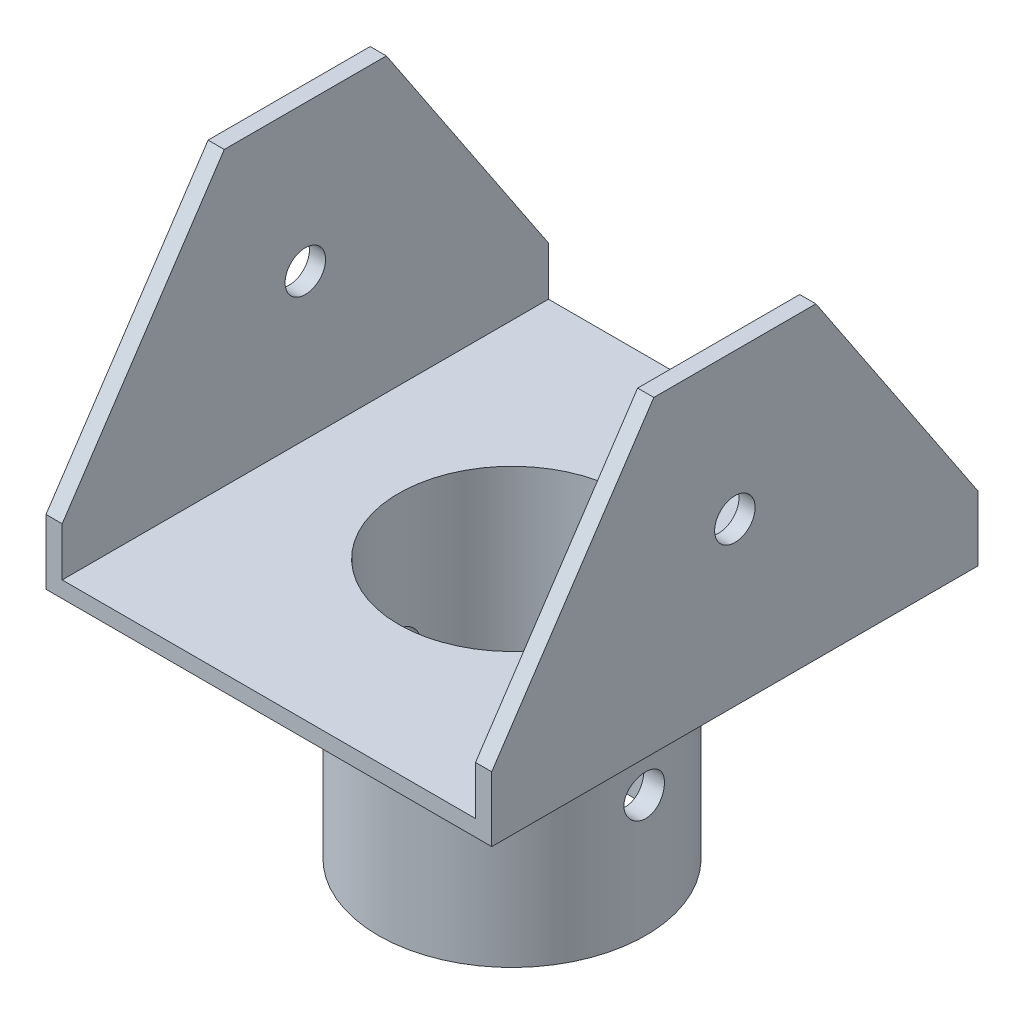
SolidWorks part; units mm, degrees
ref_plane "前视基准面" through (0, 0, 0) normal (0, 0, 1) x (1, 0, 0)
ref_plane "上视基准面" through (0, 0, 0) normal (0, 1, 0) x (1, 0, 0)
ref_plane "右视基准面" through (0, 0, 0) normal (1, 0, 0) x (0, 0, -1)
sketch "草图1" plane through (0, 0, 0) normal (0, 1, 0) x (1, 0, 0)
  circle A0 centre (0, 0) radius 14
  circle A1 centre (0, 0) radius 16.5
  dimension "D1" = 2.5
  dimension "D2" = 33
extrude "凸台-拉伸1" add sketch "草图1" along normal blind 30
sketch "草图2" plane through (0, 0, 0) normal (0, 0, 1) x (1, 0, 0)
  line L0 (0, 0) -> (0, 28.5022) construction
  line L1 (-16.5, 0) -> (16.5, 0) construction
  line L2 (27.5, 30) -> (-27.5, 30)
  line L3 (16.5, 30) -> (-16.5, 30) construction
  line L4 (-27.5, 30) -> (-27.5, 68)
  line L5 (-27.5, 68) -> (-25.5, 68)
  line L6 (-25.5, 68) -> (-25.5, 32)
  line L7 (-25.5, 32) -> (25.5, 32)
  line L9 (27.5, 30) -> (27.5, 68)
  line L10 (27.5, 68) -> (25.5, 68)
  line L11 (25.5, 68) -> (25.5, 32)
  point P13 (0, 32)
  point P14 (0, 30)
  dimension "D1" = 55
  dimension "D2" = 38
  dimension "D3" = 2
  dimension "D4" = 2
extrude "凸台-拉伸2" add sketch "草图2" along normal blind 30 and the other way blind 30
sketch "草图3" plane through (0, 30, 0) normal (0, -1, 0) x (1, 0, 0)
  circle A0 centre (0, 0) radius 14
  circle A1 centre (0, 0) radius 14 construction
extrude "切除-拉伸1" cut sketch "草图3" against normal blind 50
sketch "草图4" plane through (27.5, 0, 0) normal (1, 0, 0) x (0, 0, -1)
  line L0 (0, 68) -> (0, -12.9428) construction
  line L1 (30, 68) -> (-30, 68) construction
  line L2 (-30, 38) -> (-30, 68)
  line L3 (-30, 30) -> (-30, 68) construction
  line L4 (-30, 68) -> (-10, 68)
  line L5 (-10, 68) -> (-30, 38)
  line L6 (30, 68) -> (10, 68)
  line L7 (30, 38) -> (30, 68)
  line L8 (10, 68) -> (30, 38)
  line L9 (30, 30) -> (-30, 30) construction
  circle A0 centre (0, 50) radius 2.5
  circle A1 centre (0, 15) radius 2.5
  dimension "D4" = 5
  dimension "D5" = 5
  dimension "D6" = 15
  dimension "D1" = 20
  dimension "D2" = 8
  dimension "D3" = 20
extrude "切除-拉伸2" cut sketch "草图4" against normal through all
